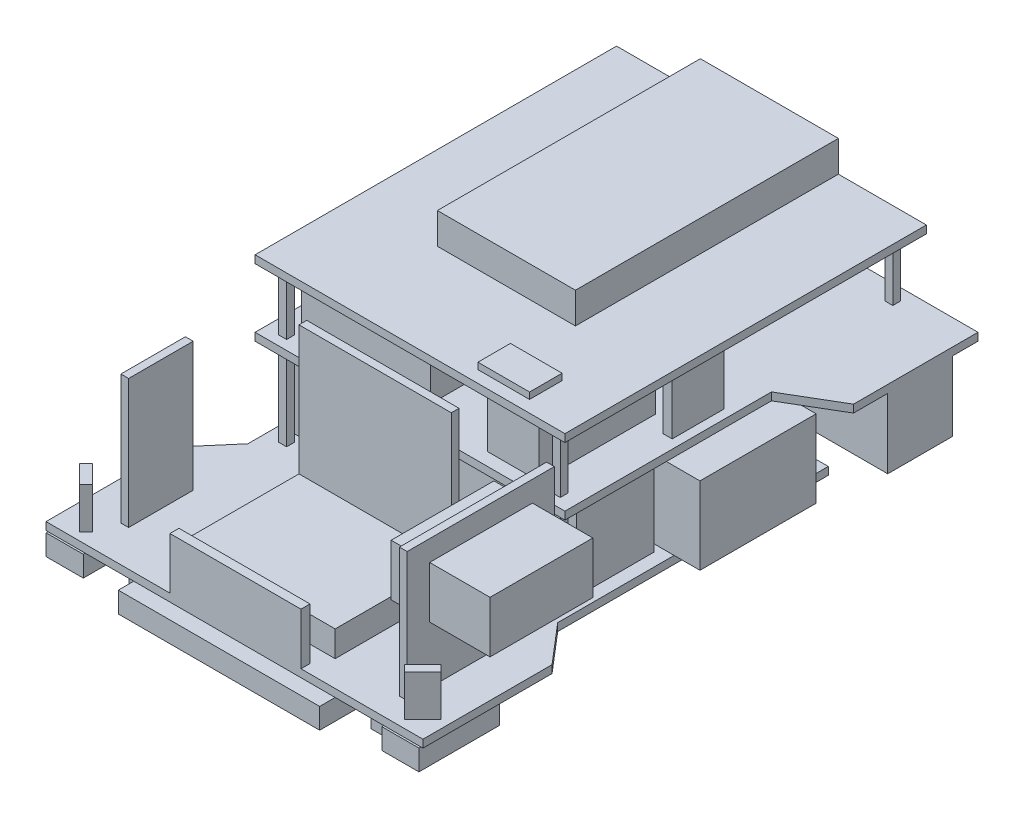
SolidWorks part; units mm, degrees
ref_plane "Front Plane" through (0, 0, 0) normal (0, 0, 1) x (1, 0, 0)
ref_plane "Top Plane" through (0, 0, 0) normal (0, 1, 0) x (1, 0, 0)
ref_plane "Right Plane" through (0, 0, 0) normal (1, 0, 0) x (0, 0, -1)
sketch "Sketch1" plane through (0, 0, 0) normal (0, 1, 0) x (1, 0, 0)
  line L0 (-73, -35) -> (-60, -19.8013)
  line L1 (60, -85) -> (-60, -85)
  line L2 (60, -19.8013) -> (60, 85)
  line L3 (60, 85) -> (-60, 85)
  line L4 (-60, -19.8013) -> (-60, 85)
  line L5 (60, -85) -> (-60, 85) construction
  line L6 (60, 85) -> (-60, -85) construction
  line L7 (0, 0) -> (0, -85) construction
  line L9 (-60, -85) -> (-73, -85)
  line L10 (-73, -35) -> (-73, -85)
  line L11 (60, -85) -> (73, -85)
  line L12 (73, -35) -> (73, -85)
  line L13 (73, -35) -> (60, -19.8013)
  point P0 (0, 0)
  dimension "D1" = 170
  dimension "D2" = 120
  dimension "D3" = 50
  dimension "D4" = 13
  dimension "D5" = 20
extrude "Boss-Extrude1" add sketch "Sketch1" along normal blind 3
sketch "Sketch2" plane through (0, 3, 0) normal (0, 1, 0) x (1, 0, 0)
  line L0 (0, 0) -> (0, 85) construction
  line L1 (60, 85) -> (-60, 85) construction
  line L2 (-60, 85) -> (-60, -19.8013) construction
  line L4 (-54.525, -13.335) -> (-51.475, -13.335)
  line L5 (-54.525, -13.335) -> (-54.525, -10.285)
  line L6 (-54.525, -10.285) -> (-51.475, -10.285)
  line L7 (-51.475, -13.335) -> (-51.475, -10.285)
  line L8 (-54.525, -13.335) -> (-51.475, -10.285) construction
  line L9 (-54.525, -10.285) -> (-51.475, -13.335) construction
  line L10 (51.475, -13.335) -> (54.525, -13.335)
  line L11 (51.475, -13.335) -> (51.475, -10.285)
  line L12 (51.475, -10.285) -> (54.525, -10.285)
  line L13 (54.525, -13.335) -> (54.525, -10.285)
  line L14 (51.475, -13.335) -> (54.525, -10.285) construction
  line L15 (51.475, -10.285) -> (54.525, -13.335) construction
  line L16 (52.475, 73.475) -> (55.525, 73.475)
  line L17 (52.475, 73.475) -> (52.475, 76.525)
  line L18 (52.475, 76.525) -> (55.525, 76.525)
  line L19 (55.525, 73.475) -> (55.525, 76.525)
  line L20 (52.475, 73.475) -> (55.525, 76.525) construction
  line L21 (52.475, 76.525) -> (55.525, 73.475) construction
  line L22 (-55.525, 73.475) -> (-52.475, 73.475)
  line L23 (-55.525, 73.475) -> (-55.525, 76.525)
  line L24 (-55.525, 76.525) -> (-52.475, 76.525)
  line L25 (-52.475, 73.475) -> (-52.475, 76.525)
  line L26 (-55.525, 73.475) -> (-52.475, 76.525) construction
  line L27 (-55.525, 76.525) -> (-52.475, 73.475) construction
  circle A0 centre (-53, -11.81) radius 1.525 construction
  circle A1 centre (-54, 75) radius 1.525 construction
  circle A2 centre (53, -11.81) radius 1.525 construction
  circle A3 centre (54, 75) radius 1.525 construction
  dimension "D1" = 10
  dimension "D2" = 3.05
  dimension "D3" = 6
  dimension "D4" = 3.05
  dimension "D5" = 7
  dimension "D6" = 86.81
extrude "Boss-Extrude2" add sketch "Sketch2" along normal blind 33
sketch "Sketch3" plane through (0, 36, 0) normal (0, 1, 0) x (1, 0, 0)
  line L0 (0, 52.99) -> (0, 122.99) construction
  line L1 (-60, -17.01) -> (60, -17.01)
  line L2 (-60, -17.01) -> (-60, 122.99)
  line L3 (-60, 122.99) -> (60, 122.99)
  line L4 (60, -17.01) -> (60, 122.99)
  line L5 (-60, -17.01) -> (60, 122.99) construction
  line L6 (-60, 122.99) -> (60, -17.01) construction
  line L7 (-60, 122.99) -> (-80, 122.99)
  line L8 (-80, 122.99) -> (-80, 74.7803)
  line L9 (-80, 74.7803) -> (-60, 62.99)
  line L10 (80, 74.7803) -> (60, 62.99)
  line L11 (80, 122.99) -> (80, 74.7803)
  line L12 (60, 122.99) -> (80, 122.99)
  line L14 (-54.525, -10.285) -> (-54.525, -13.335) construction
  point P0 (0, 52.99)
  point P19 (-54.525, -11.81)
  dimension "D1" = 120
  dimension "D2" = 140
  dimension "D3" = 60
  dimension "D4" = 30.52
  dimension "D5" = 20
  dimension "D6" = 5.2
extrude "Boss-Extrude3" add sketch "Sketch3" along normal blind 3 contours L8 L9 L2 L7 | L1 L4 L3 L2 | L12 L4 L10 L11 | L2 L1 L4 L3 region at (0, 36, -52.99) region at (-69.6368, 36, -95.8305) region at (69.6368, 36, -95.8305)
sketch "Sketch4" plane through (0, 39, 0) normal (0, 1, 0) x (1, 0, 0)
  line L0 (0, 0) -> (0, 32.3428) construction
  line L1 (-54.525, -13.335) -> (-51.475, -13.335)
  line L2 (-54.525, -13.335) -> (-54.525, -10.285)
  line L3 (-54.525, -10.285) -> (-51.475, -10.285)
  line L4 (-51.475, -13.335) -> (-51.475, -10.285)
  line L5 (-54.525, -13.335) -> (-51.475, -10.285) construction
  line L6 (-54.525, -10.285) -> (-51.475, -13.335) construction
  line L7 (-60, -17.01) -> (60, -17.01) construction
  line L8 (-60, -17.01) -> (-60, 62.99) construction
  line L9 (80, 122.99) -> (-80, 122.99) construction
  line L10 (-54.525, 115.465) -> (-51.475, 115.465)
  line L11 (-54.525, 115.465) -> (-54.525, 118.515)
  line L12 (-54.525, 118.515) -> (-51.475, 118.515)
  line L13 (-51.475, 115.465) -> (-51.475, 118.515)
  line L14 (-54.525, 115.465) -> (-51.475, 118.515) construction
  line L15 (-54.525, 118.515) -> (-51.475, 115.465) construction
  line L16 (54.525, -10.285) -> (51.475, -13.335) construction
  line L17 (54.525, -13.335) -> (51.475, -10.285) construction
  line L18 (51.475, -13.335) -> (51.475, -10.285)
  line L19 (54.525, -10.285) -> (51.475, -10.285)
  line L20 (54.525, -13.335) -> (54.525, -10.285)
  line L21 (54.525, -13.335) -> (51.475, -13.335)
  line L22 (54.525, 118.515) -> (51.475, 115.465) construction
  line L23 (54.525, 115.465) -> (51.475, 118.515) construction
  line L24 (51.475, 115.465) -> (51.475, 118.515)
  line L25 (54.525, 118.515) -> (51.475, 118.515)
  line L26 (54.525, 115.465) -> (54.525, 118.515)
  line L27 (54.525, 115.465) -> (51.475, 115.465)
  point P0 (-53, -11.81)
  point P12 (-53, 116.99)
  point P24 (53, -11.81)
  point P29 (53, 116.99)
  dimension "D1" = 3.05
  dimension "D2" = 5.2
  dimension "D3" = 7
  dimension "D4" = 6
extrude "Boss-Extrude4" add sketch "Sketch4" along normal blind 23
sketch "Sketch6" plane through (0, 62, 0) normal (0, 1, 0) x (1, 0, 0)
  line L0 (60, -17.01) -> (-60, -17.01)
  line L1 (60, -17.01) -> (60, 122.99)
  line L2 (-60, -17.01) -> (-60, 122.99)
  line L3 (60, 122.99) -> (-60, 122.99)
  line L4 (80, 122.99) -> (-80, 122.99) construction
extrude "Boss-Extrude5" add sketch "Sketch6" along normal blind 3
sketch "Sketch7" plane through (0, 36, 0) normal (0, -1, 0) x (1, 0, 0)
  line L0 (-80, -88.03) -> (-80, -113.03)
  line L1 (-80, -88.03) -> (-12, -88.03)
  line L2 (-80, -113.03) -> (-12, -113.03)
  line L3 (-12, -88.03) -> (-12, -113.03)
  line L4 (-80, -122.99) -> (-80, -74.7803) construction
  line L5 (0, 0) -> (0, -39.6137) construction
  line L6 (12, -88.03) -> (12, -113.03)
  line L7 (80, -113.03) -> (12, -113.03)
  line L8 (80, -88.03) -> (12, -88.03)
  line L9 (80, -88.03) -> (80, -113.03)
  line L10 (80, -122.99) -> (-80, -122.99) construction
  point P13 (-80, -100.53)
  dimension "D1" = 68
  dimension "D2" = 25
  dimension "D3" = 22.46
extrude "Boss-Extrude6" add sketch "Sketch7" along normal blind 27
sketch "Sketch9" plane through (0, 39, 0) normal (0, 1, 0) x (1, 0, 0)
  line L0 (-60, -17.01) -> (-60, 62.99) construction
  line L1 (-30.05, 55.88) -> (27.95, 55.88)
  line L2 (-30.05, 55.88) -> (-30.05, 115.88)
  line L3 (-30.05, 115.88) -> (27.95, 115.88)
  line L4 (27.95, 55.88) -> (27.95, 115.88)
  line L5 (-30.05, 55.88) -> (27.95, 115.88) construction
  line L6 (-30.05, 115.88) -> (27.95, 55.88) construction
  line L7 (80, 122.99) -> (-80, 122.99) construction
  line L8 (0, 0) -> (0, 23.7636) construction
  line L13 (-60, 122.99) -> (-60, -17.01) construction
  line L15 (-60, -17.01) -> (60, -17.01) construction
  line L16 (45, -12.01) -> (25, -12.01)
  line L17 (25, 32.99) -> (25, -12.01)
  line L18 (45, 32.99) -> (25, 32.99)
  line L19 (45, 32.99) -> (45, -12.01)
  line L20 (-60, -17.01) -> (60, -17.01) construction
  line L21 (-52, 22.99) -> (-2, 22.99)
  line L22 (-52, 22.99) -> (-52, -7.01)
  line L23 (-52, -7.01) -> (-2, -7.01)
  line L24 (-2, 22.99) -> (-2, -7.01)
  line L25 (-52, 22.99) -> (-2, -7.01) construction
  line L26 (-52, -7.01) -> (-2, 22.99) construction
  line L27 (60, -17.01) -> (60, 122.99) construction
  point P0 (-1.05, 85.88)
  point P23 (-27, 7.99)
  dimension "D1" = 58
  dimension "D2" = 29.95
  dimension "D3" = 60
  dimension "D4" = 7.11
  dimension "D5" = 8
  dimension "D6" = 5
  dimension "D7" = 15
  dimension "D8" = 20
  dimension "D9" = 10
  dimension "D10" = 50
  dimension "D11" = 30
  dimension "D12" = 45
extrude "Boss-Extrude7" add sketch "Sketch9" along normal blind 20
sketch "Sketch10" plane through (0, 65, 0) normal (0, 1, 0) x (1, 0, 0)
  line L0 (-27.54, 122.99) -> (25.92, 122.99)
  line L1 (-27.54, 122.99) -> (-27.54, 21.14)
  line L2 (25.92, 122.99) -> (25.92, 21.14)
  line L3 (-27.54, 21.14) -> (25.92, 21.14)
  line L4 (60, 122.99) -> (-60, 122.99) construction
  line L5 (-60, 122.99) -> (-60, -17.01) construction
  dimension "D1" = 32.46
  dimension "D2" = 53.46
  dimension "D3" = 101.85
extrude "Boss-Extrude8" add sketch "Sketch10" along normal blind 12
sketch "Sketch11" plane through (0, 3, 0) normal (0, 1, 0) x (1, 0, 0)
  line L1 (-55, 22.5437) -> (55, 22.5437)
  line L2 (-55, 22.5437) -> (-55, -7.4563)
  line L3 (-55, -7.4563) -> (55, -7.4563)
  line L4 (55, 22.5437) -> (55, -7.4563)
  line L5 (-55, 22.5437) -> (55, -7.4563) construction
  line L6 (-55, -7.4563) -> (55, 22.5437) construction
  point P0 (0, 7.5437)
  dimension "D1" = 110
  dimension "D2" = 30
extrude "Boss-Extrude9" add sketch "Sketch11" along normal blind 32
sketch "Sketch12" plane through (0, 3, 0) normal (0, 1, 0) x (1, 0, 0)
  line L1 (-70, 25.2932) -> (70, 25.2932)
  line L2 (-70, 25.2932) -> (-70, 70.2932)
  line L3 (-70, 70.2932) -> (70, 70.2932)
  line L4 (70, 25.2932) -> (70, 70.2932)
  line L5 (-70, 25.2932) -> (70, 70.2932) construction
  line L6 (-70, 70.2932) -> (70, 25.2932) construction
  point P0 (0, 47.7932)
  dimension "D1" = 140
  dimension "D2" = 45
extrude "Boss-Extrude10" add sketch "Sketch12" along normal blind 30
sketch "Sketch13" plane through (0, 65, 0) normal (0, 1, 0) x (1, 0, 0)
  line L0 (60, -17.01) -> (60, 122.99) construction
  line L1 (21.68, -12.39) -> (41.68, -12.39)
  line L2 (21.68, -12.39) -> (21.68, 0.21)
  line L3 (21.68, 0.21) -> (41.68, 0.21)
  line L4 (41.68, -12.39) -> (41.68, 0.21)
  line L5 (21.68, -12.39) -> (41.68, 0.21) construction
  line L6 (21.68, 0.21) -> (41.68, -12.39) construction
  line L7 (-60, -17.01) -> (60, -17.01) construction
  point P0 (31.68, -6.09)
  dimension "D1" = 20
  dimension "D2" = 12.6
  dimension "D3" = 18.32
  dimension "D4" = 4.62
extrude "Boss-Extrude11" add sketch "Sketch13" along normal blind 2.5
sketch "Sketch14" plane through (0, 39, 0) normal (0, 1, 0) x (1, 0, 0)
  line L0 (60, -17.01) -> (60, 122.99) construction
  line L1 (56.55, 47.99) -> (52.95, 47.99)
  line L2 (56.55, 47.99) -> (56.55, 27.99)
  line L3 (56.55, 27.99) -> (52.95, 27.99)
  line L4 (52.95, 47.99) -> (52.95, 27.99)
  line L5 (56.55, 47.99) -> (52.95, 27.99) construction
  line L6 (56.55, 27.99) -> (52.95, 47.99) construction
  line L7 (-60, -17.01) -> (60, -17.01) construction
  line L8 (0, 0) -> (0, 51.8866) construction
  line L9 (-56.55, 27.99) -> (-52.95, 47.99) construction
  line L10 (-56.55, 47.99) -> (-52.95, 27.99) construction
  line L11 (-52.95, 47.99) -> (-52.95, 27.99)
  line L12 (-56.55, 27.99) -> (-52.95, 27.99)
  line L13 (-56.55, 47.99) -> (-56.55, 27.99)
  line L14 (-56.55, 47.99) -> (-52.95, 47.99)
  point P0 (54.75, 37.99)
  point P16 (-54.75, 37.99)
  dimension "D1" = 3.45
  dimension "D2" = 7.05
  dimension "D3" = 20
  dimension "D4" = 45
extrude "Boss-Extrude12" add sketch "Sketch14" along normal blind 20
sketch "Sketch15" plane through (0, 3, 0) normal (0, 1, 0) x (1, 0, 0)
  line L6 (0, 0) -> (0, -32.3725) construction
  line L11 (62.9289, -82) -> (60.4541, -79.5251)
  line L12 (60.4541, -79.5251) -> (67.5251, -72.4541)
  line L13 (67.5251, -72.4541) -> (70, -74.9289)
  line L14 (70, -74.9289) -> (62.9289, -82)
  line L15 (-70, -74.9289) -> (-62.9289, -82)
  line L16 (-67.5251, -72.4541) -> (-70, -74.9289)
  line L17 (-60.4541, -79.5251) -> (-67.5251, -72.4541)
  line L18 (-62.9289, -82) -> (-60.4541, -79.5251)
  line L19 (-73, -85) -> (73, -85) construction
  line L20 (73, -85) -> (73, -35) construction
  dimension "D1" = 3.5
  dimension "D2" = 10
  dimension "D3" = 3
  dimension "D4" = 3
  dimension "D5" = 45
extrude "Boss-Extrude13" add sketch "Sketch15" along normal blind 16
sketch "Sketch16" plane through (0, 3, 0) normal (0, 1, 0) x (1, 0, 0)
  line L0 (73, -85) -> (73, -35) construction
  line L1 (54, -18.1) -> (57, -18.1)
  line L2 (54, -18.1) -> (54, -75.1)
  line L3 (54, -75.1) -> (57, -75.1)
  line L4 (57, -18.1) -> (57, -75.1)
  line L5 (-73, -85) -> (73, -85) construction
  line L6 (-73, -35) -> (-73, -85) construction
  line L7 (-58, -46) -> (-55, -46)
  line L8 (-58, -46) -> (-58, -71)
  line L9 (-58, -71) -> (-55, -71)
  line L10 (-55, -46) -> (-55, -71)
  dimension "D1" = 19
  dimension "D2" = 3
  dimension "D3" = 57
  dimension "D4" = 9.9
  dimension "D5" = 15
  dimension "D6" = 3
  dimension "D7" = 25
  dimension "D8" = 14
extrude "Boss-Extrude14" add sketch "Sketch16" along normal blind 50
sketch "Sketch17" plane through (57, 0, 0) normal (1, 0, 0) x (0, 0, -1)
  line L0 (-75.1, 53) -> (-18.1, 53) construction
  line L1 (-66.4113, 45) -> (-26.6028, 45)
  line L2 (-66.4113, 45) -> (-66.4113, 25)
  line L3 (-66.4113, 25) -> (-26.6028, 25)
  line L4 (-26.6028, 45) -> (-26.6028, 25)
  dimension "D1" = 8
  dimension "D2" = 20
extrude "Boss-Extrude15" add sketch "Sketch17" along normal blind 23.4 and the other way blind 14.9
sketch "Sketch18" plane through (0, 0, 0) normal (0, -1, 0) x (1, 0, 0)
  line L0 (-73, 85) -> (73, 85) construction
  line L1 (-39, 66) -> (39, 66)
  line L2 (-39, 66) -> (-39, 91)
  line L3 (-39, 91) -> (39, 91)
  line L4 (39, 66) -> (39, 91)
  line L5 (0, 85) -> (0, 37.8257) construction
  line L6 (-72.2, 85.75) -> (-57.8, 85.75)
  line L7 (-72.2, 85.75) -> (-72.2, 54.45)
  line L8 (-72.2, 54.45) -> (-57.8, 54.45)
  line L9 (-57.8, 85.75) -> (-57.8, 54.45)
  line L10 (57.8, 85.75) -> (57.8, 54.45)
  line L11 (72.2, 54.45) -> (57.8, 54.45)
  line L12 (72.2, 85.75) -> (72.2, 54.45)
  line L13 (72.2, 85.75) -> (57.8, 85.75)
  line L14 (-73, 35) -> (-73, 85) construction
  point P4 (0, 66)
  dimension "D1" = 25
  dimension "D2" = 78
  dimension "D3" = 6
  dimension "D4" = 14.4
  dimension "D5" = 31.3
  dimension "D6" = 0.8
  dimension "D7" = 0.75
extrude "Boss-Extrude16" add sketch "Sketch18" along normal blind 8
sketch "Sketch20" plane through (0, 0, 0) normal (0, -1, 0) x (1, 0, 0)
  line L0 (0, 0) -> (0, 27.2161) construction
  line L1 (-51.89, 74) -> (-41.89, 74)
  line L2 (-51.89, 74) -> (-51.89, 64)
  line L3 (-51.89, 64) -> (-41.89, 64)
  line L4 (-41.89, 74) -> (-41.89, 64)
  line L9 (41.89, 74) -> (41.89, 64)
  line L10 (51.89, 64) -> (41.89, 64)
  line L11 (51.89, 74) -> (51.89, 64)
  line L12 (51.89, 74) -> (41.89, 74)
  line L14 (80, -88.03) -> (80, -74.7803) construction
  line L15 (39, 85) -> (57.8, 85) construction
  dimension "D1" = 10
  dimension "D2" = 10
  dimension "D3" = 11
  dimension "D4" = 28.11
extrude "Boss-Extrude18" add sketch "Sketch20" along normal blind 14.56
sketch "Sketch21" plane through (0, -14.56, 0) normal (0, -1, 0) x (1, 0, 0)
  line L14 (50.89, 65) -> (50.89, 73)
  line L15 (42.89, 65) -> (50.89, 65)
  line L16 (42.89, 73) -> (42.89, 65)
  line L17 (50.89, 73) -> (42.89, 73)
  line L18 (50.89, 65) -> (50.89, 73)
  line L19 (42.89, 65) -> (50.89, 65)
  line L20 (42.89, 73) -> (42.89, 65)
  line L21 (50.89, 73) -> (42.89, 73)
  line L32 (-42.89, 65) -> (-42.89, 73)
  line L33 (-50.89, 65) -> (-42.89, 65)
  line L34 (-50.89, 73) -> (-50.89, 65)
  line L35 (-42.89, 73) -> (-50.89, 73)
  line L36 (-42.89, 65) -> (-42.89, 73)
  line L37 (-50.89, 65) -> (-42.89, 65)
  line L38 (-50.89, 73) -> (-50.89, 65)
  line L39 (-42.89, 73) -> (-50.89, 73)
  dimension "D1" = 1
  dimension "D2" = 1
extrude "Cut-Extrude1" cut sketch "Sketch21" against normal blind 5
sketch "Sketch22" plane through (0, 3, 0) normal (0, 1, 0) x (1, 0, 0)
  line L0 (-73, -35) -> (-73, -85) construction
  line L1 (-25, -81.5) -> (25.76, -81.5)
  line L2 (-25, -81.5) -> (-25, -85)
  line L3 (-25, -85) -> (25.76, -85)
  line L4 (25.76, -81.5) -> (25.76, -85)
  line L5 (73, -85) -> (73, -35) construction
  line L6 (-39, -85) -> (39, -85) construction
  dimension "D1" = 48
  dimension "D2" = 47.24
  dimension "D3" = 3.5
extrude "Boss-Extrude19" add sketch "Sketch22" along normal blind 20
sketch "Sketch23" plane through (0, 3, 0) normal (0, 1, 0) x (1, 0, 0)
  line L0 (-55, -71) -> (-55, -46) construction
  line L1 (-30, -27.01) -> (29, -27.01)
  line L2 (-30, -27.01) -> (-30, -75)
  line L3 (-30, -75) -> (29, -75)
  line L4 (29, -27.01) -> (29, -75)
  line L5 (54, -18.1) -> (54, -75.1) construction
  line L6 (-39, -85) -> (39, -85) construction
  line L7 (-60, -17.01) -> (60, -17.01) construction
  dimension "D1" = 25
  dimension "D2" = 25
  dimension "D3" = 10
  dimension "D4" = 10
extrude "Boss-Extrude20" add sketch "Sketch23" along normal blind 10
sketch "Sketch24" plane through (0, 13, 0) normal (0, 1, 0) x (1, 0, 0)
  line L0 (29, -75) -> (29, -27.01) construction
  line L1 (-30, -27.01) -> (29, -27.01)
  line L2 (-30, -27.01) -> (-30, -30.01)
  line L3 (-30, -30.01) -> (29, -30.01)
  line L4 (29, -27.01) -> (29, -30.01)
  dimension "D1" = 3
extrude "Boss-Extrude21" add sketch "Sketch24" along normal blind 50
